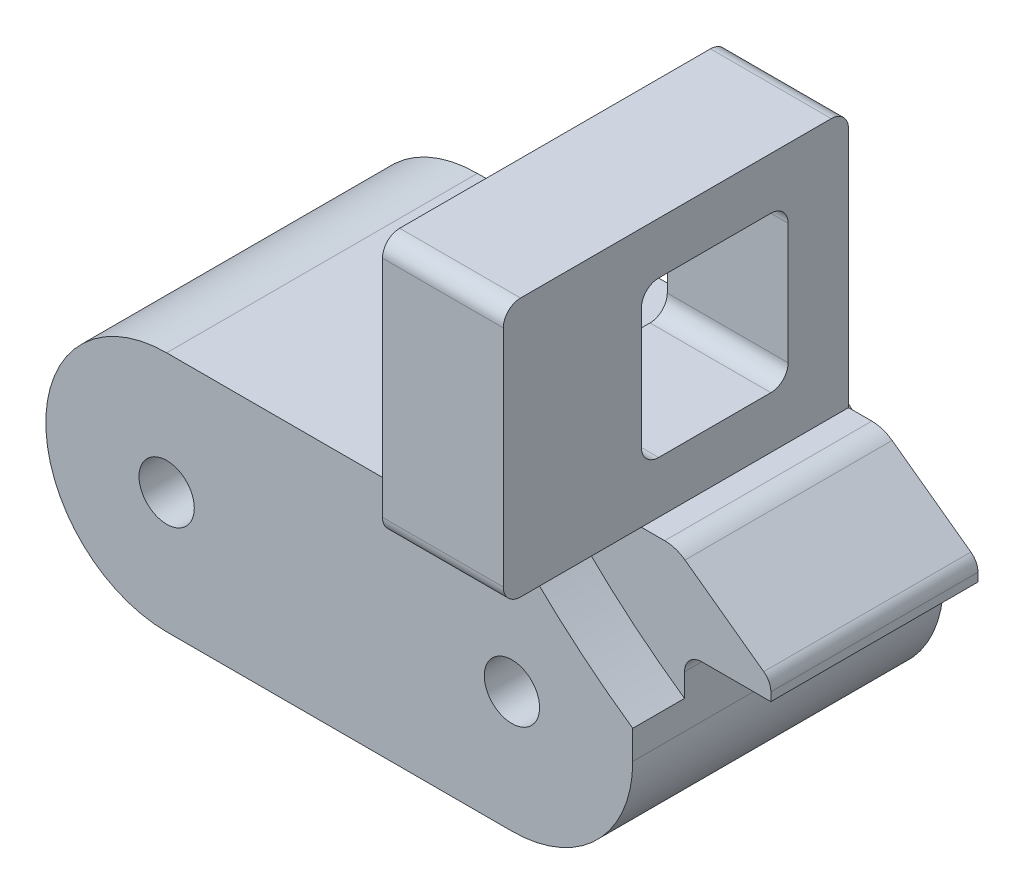
SolidWorks part; units mm, degrees
ref_plane "前视基准面" through (0, 0, 0) normal (0, 0, 1) x (1, 0, 0)
ref_plane "上视基准面" through (0, 0, 0) normal (0, 1, 0) x (1, 0, 0)
ref_plane "右视基准面" through (0, 0, 0) normal (1, 0, 0) x (0, 0, -1)
sketch "草图1" plane through (0, 0, 0) normal (0, 0, 1) x (1, 0, 0)
  line L0 (-20, 7) -> (-2.5, 7)
  line L1 (-20, -7) -> (0, -7)
  line L2 (-2.5, 7) -> (-2.5, 26)
  line L3 (-2.5, 26) -> (3.5, 26)
  line L4 (3.5, 26) -> (3.5, 9)
  line L5 (3.5, 9) -> (6.5, 9)
  line L6 (7, 4) -> (12, 4)
  line L7 (7, 0) -> (7, 4)
  line L8 (12, 4) -> (12, 5)
  line L9 (6.5, 9) -> (12, 5)
  circle A0 centre (0, 0) radius 1.6
  circle A1 centre (-20, 0) radius 1.6
  circle A2 centre (-20, 0) radius 7
  circle A3 centre (0, 0) radius 7
  dimension "D1" = 3.2
  dimension "D2" = 3.2
  dimension "D4" = 3.5
  dimension "D10" = 14
  dimension "D11" = 14
  dimension "D3" = 20
  dimension "D5" = 6
  dimension "D6" = 17
  dimension "D7" = 3
  dimension "D8" = 5
  dimension "D9" = 1
  dimension "D12" = 5
extrude "凸台-拉伸1" add sketch "草图1" along normal blind 14 contours L5 L4 L3 L2 L0 A2 L1 A3 L7 L6 | A3 A0 | A2 A1 region at (-11.25, 6.5403, 0) region at (-15.1903, 4.8097, 0) region at (-4.8097, 4.8097, 0)
fillet "圆角2" radius 1 2 edges at (7, 4, 7) (-2.5, 7, 7)
fillet "圆角4" radius 2 1 edges at (6.5, 9, 7)
fillet "圆角5" radius 1 1 edges at (12, 5, 7)
sketch "草图2" plane through (3.5, 0, 0) normal (1, 0, 0) x (0, 0, -1)
  line L0 (-7, 28.2067) -> (-7, 1.6741) construction
  line L1 (-12, 9) -> (-14, 9)
  line L2 (-14, 9) -> (0, 9) construction
  line L3 (-14, 9) -> (-14, 26)
  line L4 (-14, 26) -> (0, 26)
  line L5 (-12, 9) -> (-12, 24)
  line L6 (-12, 24) -> (-2, 24)
  line L7 (-2, 9) -> (0, 9)
  line L8 (-2, 9) -> (-2, 24)
  line L9 (0, 9) -> (0, 26)
  point P10 (-7, 24)
  point P16 (-7, 26)
  dimension "D1" = 2
  dimension "D2" = 10
extrude "切除-拉伸1" cut sketch "草图2" against normal blind 10
sketch "草图4" plane through (0, 0, 14) normal (0, 0, 1) x (1, 0, 0)
  line L1 (59.5, 65) -> (3.5, 65)
  line L2 (59.5, 65) -> (59.5, 9)
  line L3 (59.5, 9) -> (3.5, 9)
  line L4 (3.5, 65) -> (3.5, 9)
  line L5 (31.5, 9) -> (31.5, 65) construction
  line L6 (59.5, 37) -> (3.5, 37) construction
  circle A0 centre (31.5, 37) radius 43
  point P0 (31.5, 37)
  dimension "D1" = 56
  dimension "D2" = 56
extrude "切除-拉伸2" cut sketch "草图4" against normal blind 2
ref_plane "基准面1" through (0, 0, 7) normal (0, 0, 1) x (1, 0, 0)
mirror "镜向1" about plane through (0, 0, 7) normal (0, 0, 1) of "切除-拉伸2"
sketch "草图5" plane through (0, 0, 14) normal (0, 0, 1) x (1, 0, 0)
  line L5 (-1.1343, 9) -> (-2.5, 9)
  line L6 (-2.5, 9) -> (-2.5, 8)
  line L7 (-3.5, 7) -> (-20, 7)
  line L8 (-20, -7) -> (0, -7)
  line L9 (7, 0) -> (7, 1.6623)
  line L10 (-1.1343, 9) -> (-2.5, 9)
  line L11 (-2.5, 9) -> (-2.5, 8)
  line L12 (-3.5, 7) -> (-20, 7)
  line L13 (-20, -7) -> (0, -7)
  line L14 (7, 0) -> (7, 1.6623)
  circle A0 centre (0, 0) radius 1.6 construction
  circle A1 centre (-20, 0) radius 1.6 construction
  circle A2 centre (0, 0) radius 1.6
  circle A3 centre (-20, 0) radius 1.6
  arc A6 (-20, 7) -> (-20, -7) centre (-20, 0) ccw
  arc A7 (0, -7) -> (7, 0) centre (0, 0) ccw
  arc A10 (-20, 7) -> (-20, -7) centre (-20, 0) ccw
  arc A11 (0, -7) -> (7, 0) centre (0, 0) ccw
  arc A14 (-3.5, 7) -> (-2.5, 8) centre (-3.5, 8) ccw
  arc A15 (-3.5, 7) -> (-2.5, 8) centre (-3.5, 8) ccw
  arc A16 (-1.1343, 9) -> (7, 1.6623) centre (31.5, 37) ccw
  arc A20 (-1.1343, 9) -> (7, 1.6623) centre (31.5, 37) ccw
  dimension "D1" = 0
extrude "凸台-拉伸3" add sketch "草图5" along normal blind 2
sketch "草图6" plane through (0, 0, 0) normal (0, 0, -1) x (-1, 0, 0)
  line L5 (-7, 1.6623) -> (-7, 0)
  line L6 (0, -7) -> (20, -7)
  line L7 (20, 7) -> (3.5, 7)
  line L8 (2.5, 8) -> (2.5, 9)
  line L9 (2.5, 9) -> (1.1343, 9)
  line L10 (-7, 1.6623) -> (-7, 0)
  line L11 (0, -7) -> (20, -7)
  line L12 (20, 7) -> (3.5, 7)
  line L13 (2.5, 8) -> (2.5, 9)
  line L14 (2.5, 9) -> (1.1343, 9)
  circle A0 centre (20, 0) radius 1.6 construction
  circle A1 centre (0, 0) radius 1.6 construction
  circle A2 centre (20, 0) radius 1.6
  circle A3 centre (0, 0) radius 1.6
  arc A5 (-7, 0) -> (0, -7) centre (0, 0) ccw
  arc A6 (20, -7) -> (20, 7) centre (20, 0) ccw
  arc A9 (-7, 0) -> (0, -7) centre (0, 0) ccw
  arc A10 (20, -7) -> (20, 7) centre (20, 0) ccw
  arc A14 (2.5, 8) -> (3.5, 7) centre (3.5, 8) ccw
  arc A15 (2.5, 8) -> (3.5, 7) centre (3.5, 8) ccw
  arc A16 (-7, 1.6623) -> (1.1343, 9) centre (-31.5, 37) ccw
  arc A20 (-7, 1.6623) -> (1.1343, 9) centre (-31.5, 37) ccw
  dimension "D1" = 0
extrude "凸台-拉伸4" add sketch "草图6" along normal blind 2
sketch "草图8" plane through (0, 0, 12) normal (0, 0, 1) x (1, 0, 0)
  line L9 (-2.5, 9) -> (-1.1343, 9)
  line L10 (7, 1.6623) -> (7, 3)
  line L11 (8, 4) -> (12, 4)
  line L12 (12, 4) -> (12, 4.4908)
  line L13 (11.5882, 5.2995) -> (7.026, 8.6175)
  line L14 (5.8496, 9) -> (3.5, 9)
  line L15 (3.5, 9) -> (3.5, 24)
  line L16 (3.5, 24) -> (-2.5, 24)
  line L17 (-2.5, 24) -> (-2.5, 9)
  line L18 (-2.5, 9) -> (-1.1343, 9)
  line L19 (7, 1.6623) -> (7, 3)
  line L20 (8, 4) -> (12, 4)
  line L21 (12, 4) -> (12, 4.4908)
  line L22 (11.5882, 5.2995) -> (7.026, 8.6175)
  line L23 (5.8496, 9) -> (3.5, 9)
  line L24 (3.5, 9) -> (3.5, 24)
  line L25 (3.5, 24) -> (-2.5, 24)
  line L26 (-2.5, 24) -> (-2.5, 9)
  arc A4 (-1.1343, 9) -> (7, 1.6623) centre (31.5, 37) ccw
  arc A5 (8, 4) -> (7, 3) centre (8, 3) ccw
  arc A6 (12, 4.4908) -> (11.5882, 5.2995) centre (11, 4.4908) ccw
  arc A7 (7.026, 8.6175) -> (5.8496, 9) centre (5.8496, 7) ccw
  arc A8 (-1.1343, 9) -> (7, 1.6623) centre (31.5, 37) ccw
  arc A9 (8, 4) -> (7, 3) centre (8, 3) ccw
  arc A10 (12, 4.4908) -> (11.5882, 5.2995) centre (11, 4.4908) ccw
  arc A11 (7.026, 8.6175) -> (5.8496, 9) centre (5.8496, 7) ccw
  dimension "D1" = 0
extrude "凸台-拉伸6" add sketch "草图8" along normal blind 1
sketch "草图9" plane through (0, 0, 2) normal (0, 0, -1) x (-1, 0, 0)
  line L9 (-3.5, 24) -> (-3.5, 9)
  line L10 (-3.5, 9) -> (-5.8496, 9)
  line L11 (-7.026, 8.6175) -> (-11.5882, 5.2995)
  line L12 (-12, 4.4908) -> (-12, 4)
  line L13 (-12, 4) -> (-8, 4)
  line L14 (-7, 3) -> (-7, 1.6623)
  line L15 (1.1343, 9) -> (2.5, 9)
  line L16 (2.5, 9) -> (2.5, 24)
  line L17 (2.5, 24) -> (-3.5, 24)
  line L18 (-3.5, 24) -> (-3.5, 9)
  line L19 (-3.5, 9) -> (-5.8496, 9)
  line L20 (-7.026, 8.6175) -> (-11.5882, 5.2995)
  line L21 (-12, 4.4908) -> (-12, 4)
  line L22 (-12, 4) -> (-8, 4)
  line L23 (-7, 3) -> (-7, 1.6623)
  line L24 (1.1343, 9) -> (2.5, 9)
  line L25 (2.5, 9) -> (2.5, 24)
  line L26 (2.5, 24) -> (-3.5, 24)
  arc A4 (-5.8496, 9) -> (-7.026, 8.6175) centre (-5.8496, 7) ccw
  arc A5 (-11.5882, 5.2995) -> (-12, 4.4908) centre (-11, 4.4908) ccw
  arc A6 (-7, 3) -> (-8, 4) centre (-8, 3) ccw
  arc A7 (-7, 1.6623) -> (1.1343, 9) centre (-31.5, 37) ccw
  arc A8 (-5.8496, 9) -> (-7.026, 8.6175) centre (-5.8496, 7) ccw
  arc A9 (-11.5882, 5.2995) -> (-12, 4.4908) centre (-11, 4.4908) ccw
  arc A10 (-7, 3) -> (-8, 4) centre (-8, 3) ccw
  arc A11 (-7, 1.6623) -> (1.1343, 9) centre (-31.5, 37) ccw
  dimension "D1" = 0
extrude "凸台-拉伸7" add sketch "草图9" along normal blind 1
sketch "草图14" plane through (0, 0, 13) normal (0, 0, 1) x (1, 0, 0)
  line L0 (-1.1343, 9) -> (3.5, 9)
  line L9 (-2.5, 24) -> (-2.5, 9)
  line L10 (-2.5, 9) -> (-1.1343, 9)
  line L11 (7, 1.6623) -> (7, 3)
  line L12 (8, 4) -> (12, 4)
  line L13 (12, 4) -> (12, 4.4908)
  line L14 (11.5882, 5.2995) -> (7.026, 8.6175)
  line L15 (5.8496, 9) -> (3.5, 9)
  line L16 (3.5, 9) -> (3.5, 24)
  line L17 (3.5, 24) -> (-2.5, 24)
  line L18 (-2.5, 24) -> (-2.5, 9)
  line L19 (-2.5, 9) -> (-1.1343, 9)
  line L25 (3.5, 9) -> (3.5, 24)
  line L26 (3.5, 24) -> (-2.5, 24)
  arc A4 (-1.1343, 9) -> (7, 1.6623) centre (31.5, 37) ccw
  arc A5 (8, 4) -> (7, 3) centre (8, 3) ccw
  arc A6 (12, 4.4908) -> (11.5882, 5.2995) centre (11, 4.4908) ccw
  arc A7 (7.026, 8.6175) -> (5.8496, 9) centre (5.8496, 7) ccw
  dimension "D1" = 0
extrude "凸台-拉伸8" add sketch "草图14" along normal blind 8
sketch "草图13" plane through (3.5, 0, 0) normal (1, 0, 0) x (0, 0, -1)
  line L2 (-13, 20) -> (-13, 13)
  line L4 (-4.5, 13) -> (-4.5, 20)
  line L6 (-1, 24) -> (-1, 9) construction
  line L7 (-12, 21) -> (-5.5, 21)
  line L8 (-12, 12) -> (-5.5, 12)
  line L14 (-21, 24) -> (-1, 24) construction
  arc A0 (-13, 13) -> (-12, 12) centre (-12, 13) ccw
  arc A1 (-12, 21) -> (-13, 20) centre (-12, 20) ccw
  arc A2 (-5.5, 12) -> (-4.5, 13) centre (-5.5, 13) ccw
  arc A3 (-5.5, 21) -> (-4.5, 20) centre (-5.5, 20) cw
  point P8 (-9.5, 21)
  point P12 (-1, 21)
  point P16 (-9.5, 12)
  dimension "D5" = 3.5
  dimension "D6" = 1
  dimension "D7" = 1
  dimension "D8" = 1
  dimension "D9" = 1
  dimension "D1" = 9
  dimension "D2" = 3
  dimension "D3" = 8.5
  dimension "D4" = 6.5
  dimension "D10" = 6.5
extrude "切除-拉伸3" cut sketch "草图13" against normal through all
fillet "圆角6" radius 1 3 edges at (0.5, 24, 1) (0.5, 9, 21) (0.5, 24, 21)
sketch "草图16" plane through (3.5, 0, 0) normal (1, 0, 0) x (0, 0, -1)
  line L0 (-12, 12) -> (-5.5, 12) construction
  line L1 (-4.5, 13) -> (-4.5, 20) construction
  line L2 (-5.5, 21) -> (-12, 21) construction
  line L3 (-13, 20) -> (-13, 13) construction
  line L4 (-12, 12) -> (-5.5, 12)
  line L5 (-1, 9) -> (-1, 23)
  line L6 (-2, 24) -> (-20, 24)
  line L7 (-21, 23) -> (-21, 10)
  line L8 (-20, 9) -> (-13, 9)
  line L9 (-13, 9) -> (-1, 9)
  line L10 (-1, 9) -> (-1, 23)
  line L11 (-2, 24) -> (-20, 24)
  line L12 (-21, 23) -> (-21, 10)
  line L13 (-20, 9) -> (-13, 9)
  line L14 (-13, 9) -> (-1, 9)
  line L15 (-4.5, 13) -> (-4.5, 20)
  line L16 (-5.5, 21) -> (-12, 21)
  line L17 (-13, 20) -> (-13, 13)
  arc A0 (-13, 13) -> (-12, 12) centre (-12, 13) ccw construction
  arc A1 (-5.5, 12) -> (-4.5, 13) centre (-5.5, 13) ccw construction
  arc A2 (-4.5, 20) -> (-5.5, 21) centre (-5.5, 20) ccw construction
  arc A3 (-1, 23) -> (-2, 24) centre (-2, 23) ccw
  arc A4 (-20, 24) -> (-21, 23) centre (-20, 23) ccw
  arc A5 (-21, 10) -> (-20, 9) centre (-20, 10) ccw
  arc A6 (-1, 23) -> (-2, 24) centre (-2, 23) ccw
  arc A7 (-20, 24) -> (-21, 23) centre (-20, 23) ccw
  arc A8 (-21, 10) -> (-20, 9) centre (-20, 10) ccw
  arc A9 (-12, 21) -> (-13, 20) centre (-12, 20) ccw construction
  arc A10 (-13, 13) -> (-12, 12) centre (-12, 13) ccw
  arc A11 (-5.5, 12) -> (-4.5, 13) centre (-5.5, 13) ccw
  arc A12 (-4.5, 20) -> (-5.5, 21) centre (-5.5, 20) ccw
  arc A13 (-12, 21) -> (-13, 20) centre (-12, 20) ccw
  dimension "D1" = 0
extrude "凸台-拉伸10" add sketch "草图16" along normal blind 1
